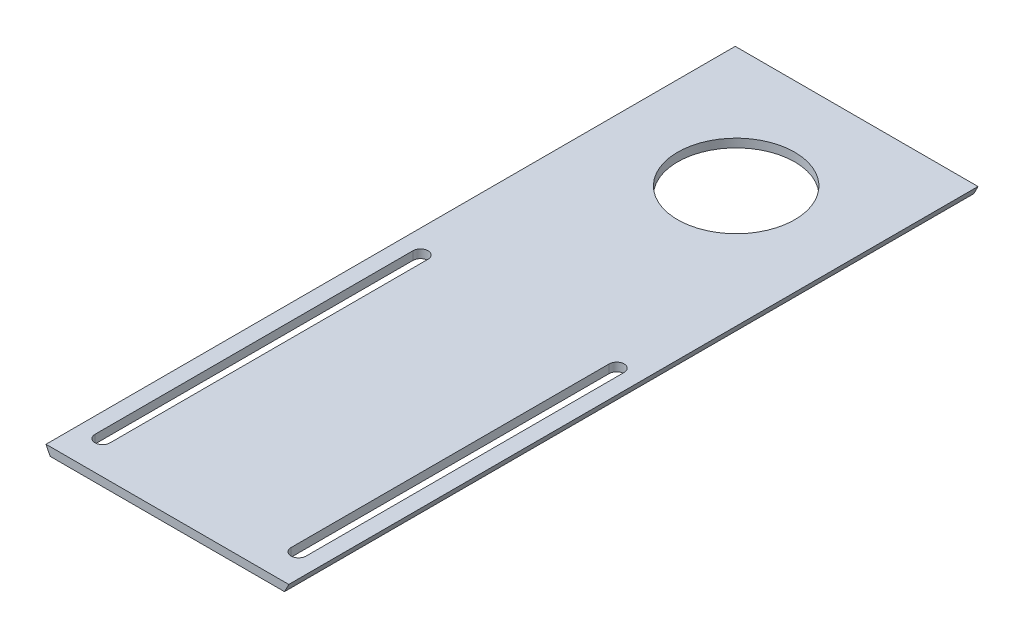
SolidWorks part; units mm, degrees
material "Brass"
ref_plane "Front Plane" through (0, 0, 0) normal (0, 0, 1) x (1, 0, 0)
ref_plane "Top Plane" through (0, 0, 0) normal (0, 1, 0) x (1, 0, 0)
ref_plane "Right Plane" through (0, 0, 0) normal (1, 0, 0) x (0, 0, -1)
sketch "Sketch2" plane through (0, 0, 0) normal (0, 0, 1) x (1, 0, 0)
  line L1 (0, -21.393) -> (0, -24.5934) construction
  line L2 (-44.45, -24.5934) -> (44.45, -24.5934)
  line L4 (-46.0758, -21.393) -> (46.0758, -21.393)
  arc A1 (-46.0758, -21.393) -> (-44.45, -24.5934) centre (0, 0) ccw
  arc A3 (44.45, -24.5934) -> (46.0758, -21.393) centre (0, 0) ccw
  dimension "D2" = 3.2004
extrude "Boss-Extrude1" add sketch "Sketch2" along normal blind 261.62 contours L4 A3 L2 A1
sketch "Sketch3" plane through (0, -24.5934, 0) normal (0, -1, 0) x (1, 0, 0)
  line L0 (-44.45, 45.72) -> (44.45, 45.72) construction
  line L1 (44.45, 261.62) -> (44.45, 0) construction
  line L2 (-44.45, 261.62) -> (-44.45, 0) construction
  line L3 (-44.45, 261.62) -> (44.45, 261.62) construction
  line L4 (0, 45.72) -> (0, 0) construction
  line L5 (-44.45, 0) -> (44.45, 0) construction
  line L6 (-40.0535, 128.3174) -> (-34.3859, 128.3174) construction
  line L7 (-40.0535, 128.3174) -> (-40.0535, 249.024)
  line L8 (-40.0535, 249.024) -> (-34.3859, 249.024) construction
  line L9 (-34.3859, 128.3174) -> (-34.3859, 249.024)
  line L10 (-37.2197, 261.62) -> (-37.2197, 251.8579) construction
  line L11 (-40.0535, 188.6707) -> (-44.45, 188.6707) construction
  line L12 (34.3859, 128.3174) -> (40.0535, 128.3174) construction
  line L13 (34.3859, 128.3174) -> (34.3859, 249.024)
  line L14 (34.3859, 249.024) -> (40.0535, 249.024) construction
  line L15 (40.0535, 128.3174) -> (40.0535, 249.024)
  line L16 (37.2197, 261.62) -> (37.2197, 251.8579) construction
  line L17 (44.45, 188.6707) -> (40.0535, 188.6707) construction
  circle A0 centre (0, 45.72) radius 22.225
  arc A1 (-40.0535, 249.024) -> (-34.3859, 249.024) centre (-37.2197, 249.024) cw
  arc A2 (-34.3859, 128.3174) -> (-40.0535, 128.3174) centre (-37.2197, 128.3174) cw
  arc A3 (34.3859, 249.024) -> (40.0535, 249.024) centre (37.2197, 249.024) cw
  arc A4 (40.0535, 128.3174) -> (34.3859, 128.3174) centre (37.2197, 128.3174) cw
  dimension "D1" = 44.45
  dimension "D2" = 45.72
  dimension "D3" = 120.7066
  dimension "D4" = 5.6676
  dimension "D5" = 9.7621
  dimension "D6" = 4.3965
  dimension "D7" = 120.7066
  dimension "D8" = 5.6676
  dimension "D9" = 9.7621
  dimension "D10" = 4.3965
extrude "Cut-Extrude1" cut sketch "Sketch3" against normal through all
